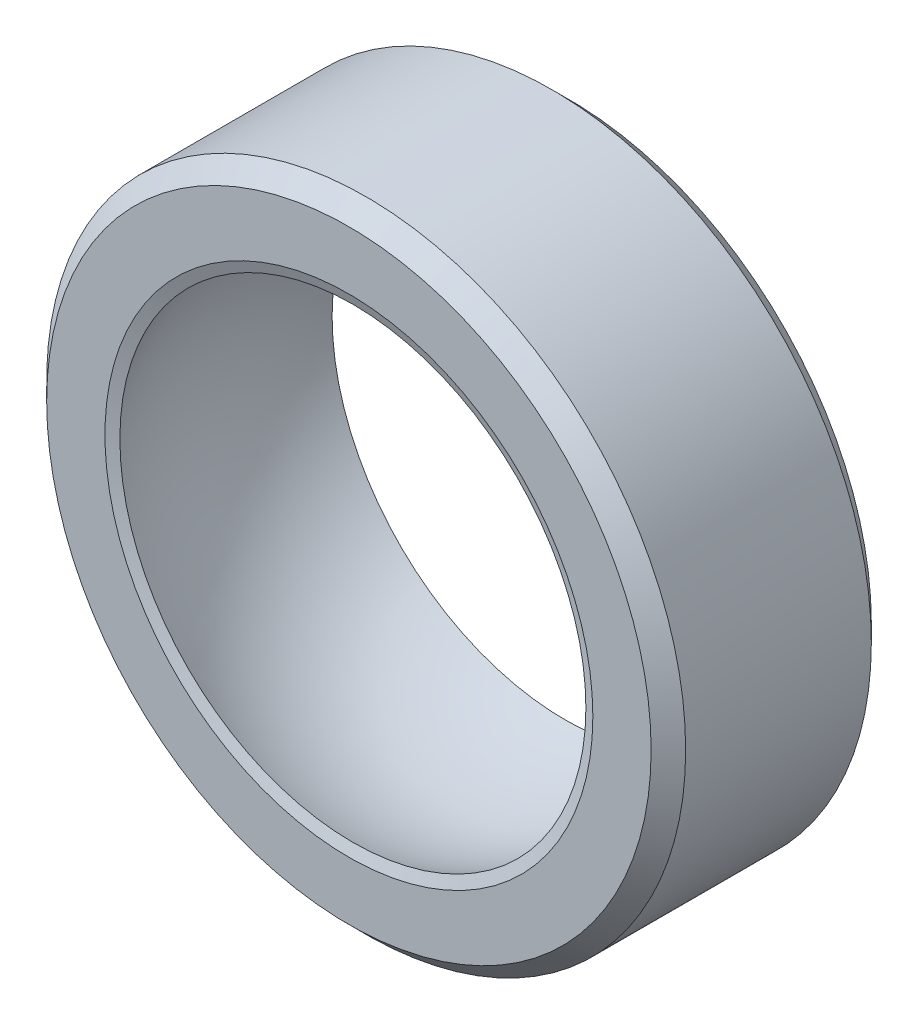
SolidWorks part; units mm, degrees
material "Chrome Stainless Steel"
ref_plane "Front Plane" through (0, 0, 0) normal (0, 0, 1) x (1, 0, 0)
ref_plane "Top Plane" through (0, 0, 0) normal (0, 1, 0) x (1, 0, 0)
ref_plane "Right Plane" through (0, 0, 0) normal (1, 0, 0) x (0, 0, -1)
sketch "Sketch1" plane through (0, 0, 0) normal (0, 1, 0) x (1, 0, 0)
  line L0 (0, -3) -> (0, 3) construction
  line L1 (-9.398, 2.7305) -> (-9.398, -2.7305)
  line L2 (-9.398, 2.7305) -> (-8.89, 3.2385)
  line L3 (-9.398, -2.7305) -> (-8.89, -3.2385)
  line L4 (-8.89, 3.2385) -> (-7.1758, 3.2385)
  line L5 (-8.89, -3.2385) -> (-7.1758, -3.2385)
  line L6 (-7.1758, 3.2385) -> (-6.8539, 3.1214)
  line L7 (-7.1758, -3.2385) -> (-6.8539, -3.1214)
  arc A0 (-6.8539, 3.1214) -> (-6.8539, -3.1214) centre (0, 0) ccw
  point P2 (-9.398, 0)
  point P13 (0, 0)
  dimension "D1" = 5.461
  dimension "D2" = 1.7142
  dimension "D3" = 0.3219
  dimension "D4" = 0.1171
  dimension "D5" = 0.508
  dimension "D6" = 0.508
  dimension "D7" = 0.508
  dimension "D8" = 0.3219
  dimension "D9" = 0.1171
  dimension "D10" = 6
  dimension "D11" = 9.398
revolve "Revolve1" add sketch "Sketch1" angle 360 about L0
ref_axis "Axis1" through (0, 0, -2.7305) along (0, 0, 1)
equation "\"D11@Sketch1\"=9.398mm"
